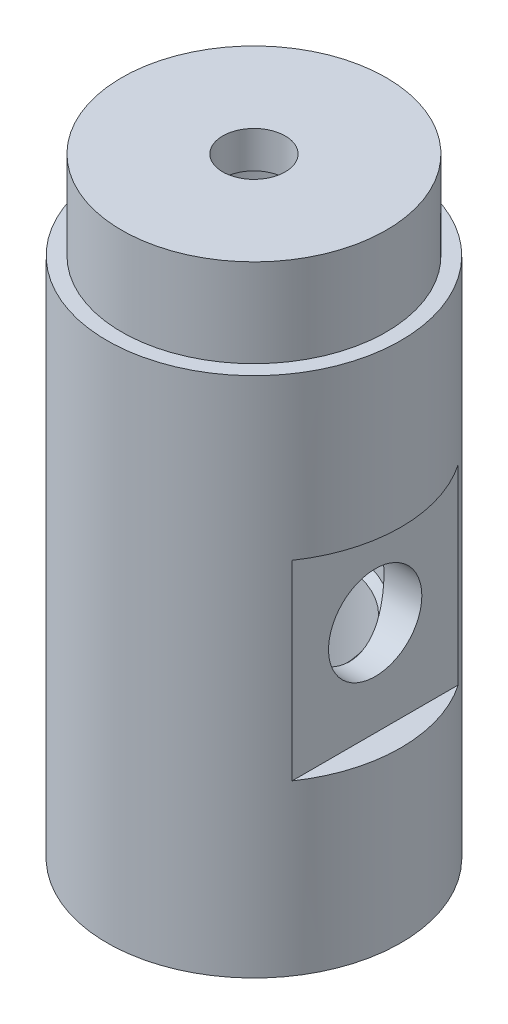
SolidWorks part; units mm, degrees
material "6061-T6 (SS)"
ref_plane "Piano frontale" through (0, 0, 0) normal (0, 0, 1) x (1, 0, 0)
ref_plane "Piano superiore" through (0, 0, 0) normal (0, 1, 0) x (1, 0, 0)
ref_plane "Piano destro" through (0, 0, 0) normal (1, 0, 0) x (0, 0, -1)
sketch "Schizzo1" plane through (0, 0, 0) normal (0, 0, 1) x (1, 0, 0)
  line L0 (0, 0) -> (0, 31.0712) construction
  line L1 (-12, 0) -> (-20, 0)
  line L2 (-20, 0) -> (-20, 71)
  line L3 (-20, 71) -> (-18, 71)
  line L4 (-18, 71) -> (-18, 83)
  line L5 (-18, 83) -> (-4.25, 83)
  line L6 (-4.25, 83) -> (-4.25, 78)
  line L7 (-4.25, 78) -> (-12, 78)
  line L8 (-12, 78) -> (-12, 0)
  dimension "D1" = 24
  dimension "D2" = 40
  dimension "D3" = 36
  dimension "D4" = 5
  dimension "D5" = 78
  dimension "D6" = 12
  dimension "D7" = 8.5
revolve "Rivoluzione1" add sketch "Schizzo1" angle 360 about L0
ref_plane "Piano1" through (20, 0, 0) normal (1, 0, 0) x (0, 0, -1)
ref_plane "Piano2" through (-20, 0, 0) normal (-1, 0, 0) x (0, 0, 1)
sketch "Schizzo4" plane through (20, 0, 0) normal (1, 0, 0) x (0, 0, -1)
  line L0 (0, 0) -> (0, 36) construction
  line L1 (13, 49) -> (-13, 49)
  line L2 (13, 49) -> (13, 23)
  line L3 (13, 23) -> (-13, 23)
  line L4 (-13, 49) -> (-13, 23)
  line L5 (13, 49) -> (-13, 23) construction
  line L6 (13, 23) -> (-13, 49) construction
  point P0 (0, 36)
  dimension "D1" = 36
  dimension "D2" = 26
extrude "Taglio-Estrusione1" cut sketch "Schizzo4" against normal blind 3.5
sketch "Schizzo5" plane through (16.5, 0, 0) normal (1, 0, 0) x (0, 0, -1)
  circle A0 centre (0, 36) radius 6.35
  point P2 (0, 0)
  dimension "D1" = 12.7
extrude "Taglio-Estrusione2" cut sketch "Schizzo5" against normal blind 9
mirror "Specchia1" about plane through (0, 0, 0) normal (1, 0, 0) of "Taglio-Estrusione1"
sketch "Schizzo6" plane through (-16.5, 0, 0) normal (-1, 0, 0) x (0, 0, 1)
  circle A0 centre (0, 36) radius 6.35
  dimension "D1" = 12.7
extrude "Taglio-Estrusione3" cut sketch "Schizzo6" against normal blind 9 contours A0
sketch "Schizzo7" plane through (0, 0, 0) normal (0, 0, 1) x (1, 0, 0)
  line L0 (-12, 42.35) -> (-12, 43.35)
  line L1 (-12, 78) -> (-12, 0) construction
  line L2 (-12, 43.35) -> (-13, 42.35)
  line L3 (-13, 42.35) -> (-12, 42.35)
  line L4 (-16.5, 42.35) -> (-12, 42.35) construction
  line L5 (-16.5, 42.35) -> (-16.5, 29.65) construction
  line L6 (-12, 36) -> (-27.6175, 36) construction
  line L7 (-16.5, 42.35) -> (-16.5, 29.65)
  line L8 (-16.5, 42.35) -> (-16.5, 29.65) construction
  line L9 (-16.5, 49) -> (-16.5, 23) construction
  line L10 (-12, 42.35) -> (-16.5, 42.35)
  line L11 (-16.5, 29.65) -> (-12, 29.65)
  line L12 (-16.5, 29.65) -> (-12, 29.65)
  line L13 (-12, 42.35) -> (-16.5, 42.35)
  line L14 (-13, 29.65) -> (-12, 29.65)
  line L15 (-12, 28.65) -> (-13, 29.65)
  line L16 (-12, 29.65) -> (-12, 28.65)
  line L17 (-13, 29.65) -> (-12, 29.65)
  line L18 (-13, 29.65) -> (-13, 42.35)
  line L19 (-12, 29.65) -> (-12, 42.35)
  spline S0 degree 2 poles (-12, 42.35) (-8.6398, 36) (-12, 29.65) knots 0 0 0 1 1 1 weights 0.00565 0.012 0.01835 construction
  point P20 (-16.5, 36)
  dimension "D1" = 1
revolve "Taglia-Rivoluzione3" cut sketch "Schizzo7" angle 360 about L0 region at (-12.3333, 42.6833, 0) region at (-12.5, 36, 0) region at (-12.3333, 29.3167, 0)
chamfer "Smusso1" distance 1 angle 45 1 edges at (0, 0, -12)
